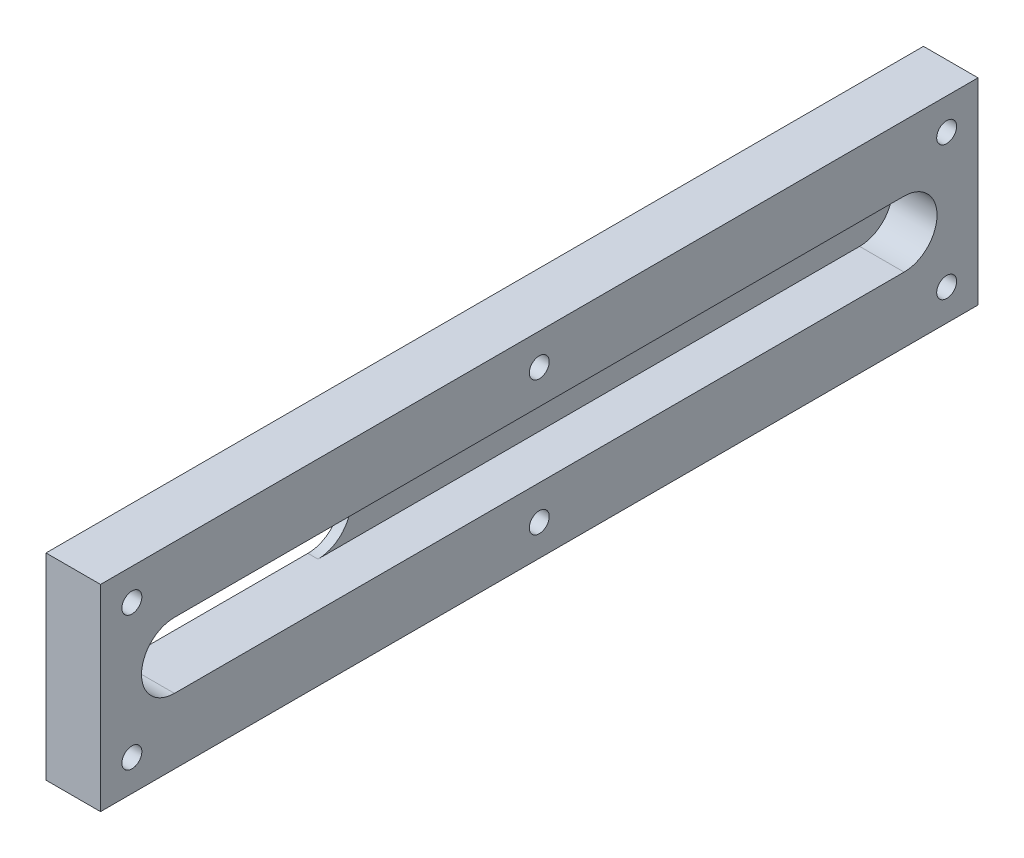
SolidWorks part; units mm, degrees
material "Delrin 2700 NC010, Low Viscosity Acetal Copolymer (SS)"
ref_plane "Front" through (0, 0, 0) normal (0, 0, 1) x (1, 0, 0)
ref_plane "Top" through (0, 0, 0) normal (0, 1, 0) x (1, 0, 0)
ref_plane "Right" through (0, 0, 0) normal (1, 0, 0) x (0, 0, -1)
sketch "Sketch1" plane through (0, 0, 0) normal (1, 0, 0) x (0, 0, -1)
  line L0 (-73.9253, 0) -> (73.9253, 0) construction
  line L1 (88.9, -19.939) -> (-88.9, -19.939)
  line L2 (88.9, -19.939) -> (88.9, 19.939)
  line L3 (88.9, 19.939) -> (-88.9, 19.939)
  line L4 (-88.9, -19.939) -> (-88.9, 19.939)
  line L5 (88.9, -19.939) -> (-88.9, 19.939) construction
  line L6 (88.9, 19.939) -> (-88.9, -19.939) construction
  line L7 (-73.9253, 6.6675) -> (73.9253, 6.6675)
  line L8 (-73.9253, -6.6675) -> (73.9253, -6.6675)
  arc A0 (-73.9253, 6.6675) -> (-73.9253, -6.6675) centre (-73.9253, 0) ccw
  arc A1 (73.9253, -6.6675) -> (73.9253, 6.6675) centre (73.9253, 0) ccw
  point P0 (0, 0)
  point P8 (0, 0)
  dimension "D4" = 13.335
  dimension "D1" = 147.8505
  dimension "D2" = 177.8
  dimension "D3" = 39.878
extrude "Boss-Extrude1" add sketch "Sketch1" along normal blind 11.049
hole_wizard "#10-32 Tapped Hole1" positions "Sketch3" profile "Sketch4" tap size "#10-32" standard "ANSI Inch" end condition through all
sketch "Sketch3" plane through (11.049, 0, 0) normal (1, 0, 0) x (0, 0, -1)
  line L0 (-82.55, 13.589) -> (0, 13.589) construction
  line L1 (0, 13.589) -> (82.55, 13.589) construction
  line L3 (-82.55, 19.939) -> (-82.55, 13.589) construction
  line L4 (88.9, 19.939) -> (-88.9, 19.939) construction
  line L5 (-82.55, 13.589) -> (-82.55, -13.589) construction
  line L6 (-82.55, -13.589) -> (-82.55, -19.939) construction
  line L7 (-88.9, -19.939) -> (88.9, -19.939) construction
  line L8 (-88.9, 19.939) -> (-88.9, -19.939) construction
  point P0 (-82.55, 13.589)
  point P2 (-82.55, -13.589)
  point P4 (0, -13.589)
  point P6 (82.55, -13.589)
  point P8 (82.55, 13.589)
  point P10 (0, 13.589)
  dimension "D1" = 6.35
  dimension "D2" = 6.35
sketch "Sketch4" plane through (11.049, 13.589, 82.55) normal (0, 1, 0) x (0, 0, -1)
  line L0 (0, 0) -> (0, 11.049)
  line L1 (0, 11.049) -> (2.0193, 11.049)
  line L2 (2.0193, 11.049) -> (2.0193, 0)
  line L5 (2.0193, 0) -> (0, 0)
  line L11 (0, -6.35) -> (0, 107.95) construction
  dimension "Thru Tap Drill Dia." = 4.0386
  dimension "Thru Tap Drill Depth" = 11.049
cosmetic thread "Hole Thread1" parameters "D2"=4.826
cosmetic thread "Hole Thread2" parameters "D2"=4.826
cosmetic thread "Hole Thread3" parameters "D2"=4.826
cosmetic thread "Hole Thread4" parameters "D2"=4.826
cosmetic thread "Hole Thread5" parameters "D2"=4.826
cosmetic thread "Hole Thread6" parameters "D2"=4.826
sketch "Sketch5" plane through (0, 0, 0) normal (-1, 0, 0) x (0, 0, 1)
  line L2 (-73.9253, -6.6675) -> (73.9253, -6.6675)
  line L3 (73.9253, 6.6675) -> (-73.9253, 6.6675)
  line L4 (-73.9253, -6.6675) -> (35.8253, -6.6675)
  line L5 (35.8253, 6.6675) -> (-73.9253, 6.6675)
  arc A0 (35.8253, 6.6675) -> (35.8253, -6.6675) centre (35.8253, 0) ccw
  arc A1 (73.9253, -6.6675) -> (73.9253, 6.6675) centre (73.9253, 0) ccw construction
  arc A2 (73.9253, -6.6675) -> (73.9253, 6.6675) centre (73.9253, 0) ccw
  arc A3 (-73.9253, 6.6675) -> (-73.9253, -6.6675) centre (-73.9253, 0) ccw
  arc A5 (-73.9253, 6.6675) -> (-73.9253, -6.6675) centre (-73.9253, 0) ccw
  dimension "D2" = 38.1
  dimension "D1" = 0
extrude "Boss-Extrude2" add sketch "Sketch5" against normal blind 2.032
